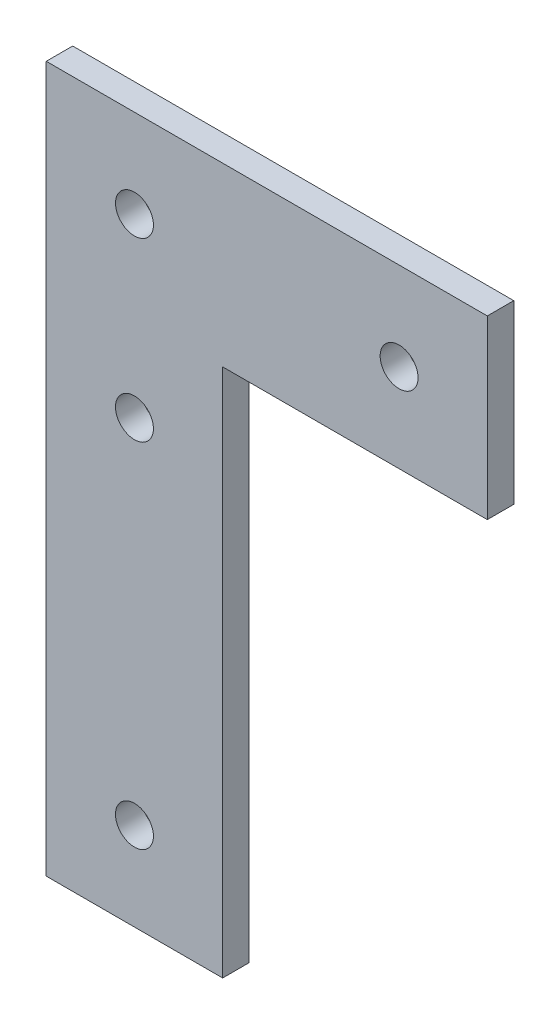
SolidWorks part; units mm, degrees
material "Thornel Mat VMA"
ref_plane "Front Plane" through (0, 0, 0) normal (0, 0, 1) x (1, 0, 0)
ref_plane "Top Plane" through (0, 0, 0) normal (0, 1, 0) x (1, 0, 0)
ref_plane "Right Plane" through (0, 0, 0) normal (1, 0, 0) x (0, 0, -1)
sketch "Sketch1" plane through (0, 0, 0) normal (0, 0, 1) x (1, 0, 0)
  line L0 (-350.6121, 147.905) -> (329.3879, 147.905) construction
  line L1 (-300.6121, 147.905) -> (-350.6121, 147.905)
  line L2 (-300.6121, 147.905) -> (-300.6121, 127.905)
  line L3 (-300.6121, 127.905) -> (-330.6121, 127.905)
  line L4 (-350.6121, 147.905) -> (-350.6121, 127.905)
  line L5 (-350.6121, -492.095) -> (-350.6121, 147.905) construction
  line L6 (-350.6121, 67.905) -> (-350.6121, 147.905) construction
  line L7 (-350.6121, 67.905) -> (-330.6121, 67.905)
  line L8 (-350.6121, 67.905) -> (-350.6121, 127.905)
  line L10 (-330.6121, 67.905) -> (-330.6121, 127.905)
  line L11 (-330.6121, 67.905) -> (-350.6121, 67.905) construction
  line L12 (-300.6121, 147.905) -> (-300.6121, 127.905) construction
  line L13 (-350.6121, 147.905) -> (-300.6121, 147.905) construction
  circle A0 centre (-340.6121, 77.905) radius 2.15 construction
  circle A1 centre (-340.6121, 117.905) radius 2.15 construction
  circle A2 centre (-340.6121, 137.905) radius 2.15 construction
  circle A3 centre (-310.6121, 137.905) radius 2.15 construction
  circle A4 centre (-340.6121, 77.905) radius 2.15
  circle A5 centre (-340.6121, 117.905) radius 2.15
  circle A6 centre (-340.6121, 137.905) radius 2.15
  circle A7 centre (-310.6121, 137.905) radius 2.15
extrude "Extrude1" add sketch "Sketch1" along normal blind 3
